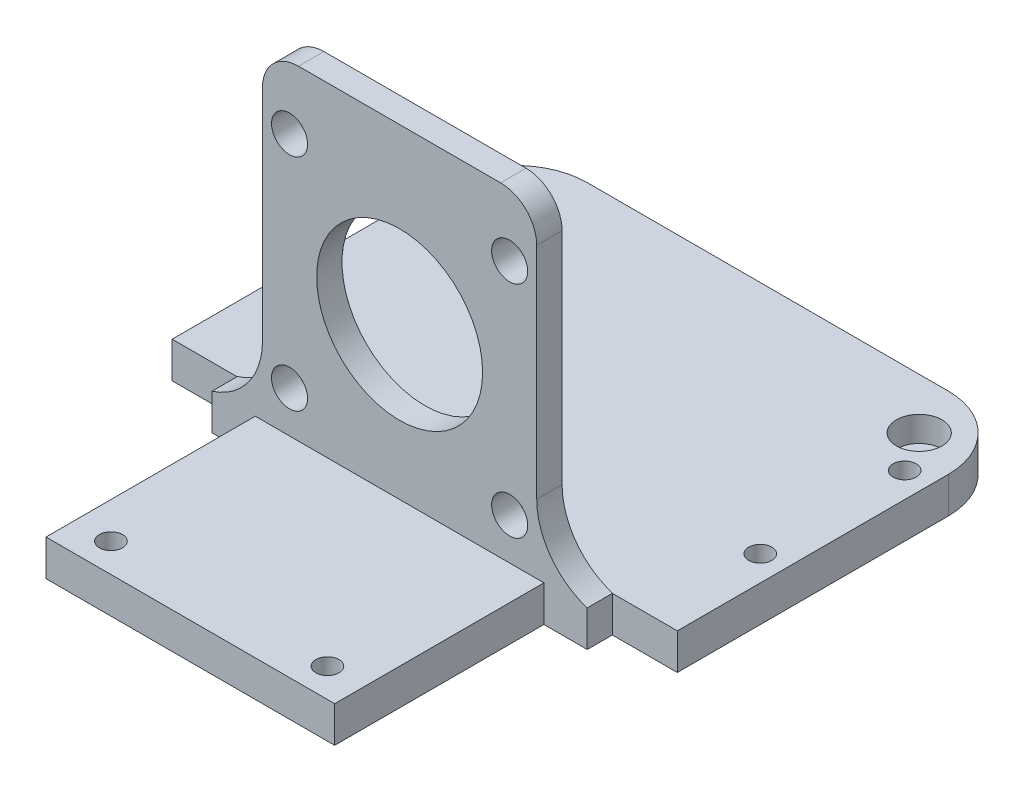
SolidWorks part; units mm, degrees
ref_plane "Front Plane" through (0, 0, 0) normal (0, 0, 1) x (1, 0, 0)
ref_plane "Top Plane" through (0, 0, 0) normal (0, 1, 0) x (1, 0, 0)
ref_plane "Right Plane" through (0, 0, 0) normal (1, 0, 0) x (0, 0, -1)
sketch "草图1" plane through (0, 0, 0) normal (0, 0, 1) x (1, 0, 0)
  line L1 (-35, 2.5) -> (35, 2.5)
  line L2 (-35, 2.5) -> (-35, -2.5)
  line L3 (-35, -2.5) -> (35, -2.5)
  line L4 (35, 2.5) -> (35, -2.5)
  line L5 (-35, 2.5) -> (35, -2.5) construction
  line L6 (-35, -2.5) -> (35, 2.5) construction
  point P0 (0, 0)
  dimension "D1" = 5
  dimension "D2" = 70
extrude "凸台-拉伸1" add sketch "草图1" along normal blind 8
sketch "草图2" plane through (0, 2.5, 0) normal (0, 1, 0) x (1, 0, 0)
  line L0 (0, 0) -> (0, -8) construction
  line L1 (35, -8) -> (-35, -8) construction
  circle A0 centre (-23.5, -4.24) radius 1.6424
  circle A1 centre (23.5, -4.24) radius 1.6424
  dimension "D1" = 23.5
  dimension "D2" = 3.76
extrude "切除-拉伸1" [suppressed] cut sketch "草图2" against normal blind 10
sketch "草图3" plane through (0, 0, 8) normal (0, 0, 1) x (1, 0, 0)
  line L0 (-35, -2.5) -> (35, -2.5) construction
  line L1 (-19, 2.5) -> (19, 2.5)
  line L2 (-19, 2.5) -> (-19, -2.5)
  line L3 (-19, -2.5) -> (19, -2.5)
  line L4 (19, 2.5) -> (19, -2.5)
  line L5 (-19, 2.5) -> (19, -2.5) construction
  line L6 (-19, -2.5) -> (19, 2.5) construction
  point P0 (0, 0)
  dimension "D1" = 38
extrude "凸台-拉伸2" add sketch "草图3" along normal blind 43
sketch "草图4" plane through (0, 2.5, 0) normal (0, 1, 0) x (1, 0, 0)
  line L0 (19, -51) -> (19, -8) construction
  line L1 (-19, -51) -> (19, -51)
  line L2 (-19, -51) -> (-19, -46)
  line L3 (-19, -46) -> (19, -46)
  line L4 (19, -51) -> (19, -46)
  dimension "D1" = 5
extrude "凸台-拉伸3" add sketch "草图4" along normal blind 45
sketch "草图5" plane through (0, 0, 51) normal (0, 0, 1) x (1, 0, 0)
  line L0 (-19, 2.5) -> (19, 2.5) construction
  line L1 (19, -2.5) -> (19, 47.5) construction
  line L2 (0, 2.5) -> (0, 44.5) construction
  circle A0 centre (0, 23.5) radius 11.5
  circle A1 centre (-15.25, 38.75) radius 1.6
  circle A2 centre (15.25, 38.75) radius 1.6
  circle A3 centre (-15.25, 8.25) radius 1.6
  circle A4 centre (15.25, 8.25) radius 1.6
  dimension "D2" = 23
  dimension "D7" = 3.2
  dimension "D1" = 42
  dimension "D3" = 15.25
  dimension "D4" = 15.25
  dimension "D5" = 15.25
  dimension "D6" = 30.5
extrude "切除-拉伸2" cut sketch "草图5" against normal blind 45
fillet "圆角1" radius 5 2 edges at (19, 47.5, 48.5) (-19, 47.5, 48.5)
sketch "草图6" plane through (0, 47.5, 0) normal (0, 1, 0) x (1, 0, 0)
  line L0 (-21, -47.4848) -> (-21, -9.4848) construction
  line L1 (21, -47.4848) -> (-21, -47.4848)
  line L2 (21, -47.4848) -> (21, -45.9222)
  line L3 (21, -45.9222) -> (-21, -45.9222)
  line L4 (-21, -47.4848) -> (-21, -45.9222)
extrude "切除-拉伸3" cut sketch "草图6" against normal up to surface (45 mm away) up to face at (0, 2.5, 15.5)
sketch "草图7" plane through (19, 0, 0) normal (1, 0, 0) x (0, 0, -1)
  line L0 (-37.9952, 2.5) -> (-37.9952, -2.5) construction
  line L1 (-51, -2.5) -> (-37.9952, -2.5)
  line L2 (-51, -2.5) -> (-51, 2.5)
  line L3 (-51, 2.5) -> (-37.9952, 2.5)
  line L4 (-37.9952, -2.5) -> (-37.9952, 2.5)
extrude "凸台-拉伸4" add sketch "草图7" along normal blind 7 and the other way blind 45
sketch "草图8" plane through (0, 2.5, 0) normal (0, 1, 0) x (1, 0, 0)
  circle A0 centre (23, -44.3286) radius 1.6
  circle A1 centre (-23, -44.3286) radius 1.6
  dimension "D1" = 3.2
extrude "切除-拉伸4" [suppressed] cut sketch "草图8" against normal blind 7
fillet "圆角2" radius 10 2 edges at (-19, 2.5, 49.2424) (19, 2.5, 49.2424)
sketch "草图9" plane through (0, 2.5, 0) normal (0, 1, 0) x (1, 0, 0)
  line L0 (-19, -8) -> (19, -8) construction
  line L1 (0, -8) -> (0, -37.9952) construction
  line L3 (-18.1552, -8) -> (18.1552, -8)
  line L4 (-18.1552, -8) -> (-18.1552, -37.9952)
  line L5 (-18.1552, -37.9952) -> (18.1552, -37.9952)
  line L6 (18.1552, -8) -> (18.1552, -37.9952)
  line L7 (-18.1552, -8) -> (18.1552, -37.9952) construction
  line L8 (-18.1552, -37.9952) -> (18.1552, -8) construction
  line L9 (-19, -8) -> (19, -8)
  line L10 (-19, -8) -> (-19, -37.9952)
  line L11 (-19, -37.9952) -> (19, -37.9952)
  line L12 (19, -8) -> (19, -37.9952)
  point P7 (0, -22.9976)
  line M9 (19, -37.9952) -> (19, -8)
  line M15 (-19, -8) -> (-19, -37.9952)
extrude "切除-拉伸5" [suppressed] cut sketch "草图9" against normal blind 10 contours L11 L4 L9 M15 | L6 L11 L9 M9
sketch "草图10" plane through (0, 0, 51) normal (0, 0, 1) x (1, 0, 0)
  circle A0 centre (-15.25, 38.75) radius 2.5
  circle A1 centre (0, 23.5) radius 21.5668 construction
  circle A2 centre (15.25, 38.75) radius 2.5
  circle A3 centre (15.25, 8.25) radius 2.5
  circle A4 centre (-15.25, 8.25) radius 2.5
  point P15 (0, 23.5)
  dimension "D1" = 5
  dimension "D2" = 4
sketch "草图13" plane through (0, 2.5, 0) normal (0, 1, 0) x (1, 0, 0)
  line L0 (0, 0) -> (0, -47.4848) construction
  line L1 (-14, -47.4848) -> (14, -47.4848) construction
  line L2 (-35, -8) -> (-35, 0) construction
  line L3 (-35, 0.0318) -> (35, 0.0318)
  line L4 (-35, 0.0318) -> (-35, -47.5165)
  line L5 (-35, -47.5165) -> (35, -47.5165)
  line L6 (35, 0.0318) -> (35, -47.5165)
  line L7 (-35, 0.0318) -> (35, -47.5165) construction
  line L8 (-35, -47.5165) -> (35, 0.0318) construction
  point P5 (0, -23.7424)
extrude "凸台-拉伸6" add sketch "草图13" against normal up to surface (5 mm away) up to face at (0, -2.5, 23.8317)
extrude "切除-拉伸6" cut sketch "草图10" against normal blind 10
sketch "草图11" plane through (0, 0, 51) normal (0, 0, 1) x (1, 0, 0)
  line L0 (0, 2.5) -> (0, 43.6627) construction
  line L2 (20, -2.5) -> (20, 2.5)
  line L3 (20, -2.5) -> (-20, -2.5)
  line L5 (20, 2.5) -> (-20, 2.5)
  line L6 (-20, -2.5) -> (-20, 2.5)
  dimension "D1" = 5
  dimension "D2" = 20
extrude "凸台-拉伸5" add sketch "草图11" along normal blind 29
sketch "草图12" plane through (0, 2.5, 0) normal (0, 1, 0) x (1, 0, 0)
  circle A0 centre (15, -76) radius 1.6
  circle A1 centre (-15, -76) radius 1.6
extrude "切除-拉伸7" cut sketch "草图12" against normal blind 7
sketch "草图14" plane through (0, 2.5, 0) normal (0, 1, 0) x (1, 0, 0)
  circle A0 centre (28, -7) radius 1.6
  circle A1 centre (-28, -7) radius 1.6
extrude "切除-拉伸8" cut sketch "草图14" against normal blind 7
sketch "草图15" plane through (0, 2.5, 0) normal (0, 1, 0) x (1, 0, 0)
  circle A0 centre (28, -7) radius 3.15
  circle A1 centre (-28, -7) radius 3.15
extrude "切除-拉伸9" cut sketch "草图15" against normal blind 3.5
fillet "圆角3" radius 10 2 edges at (35, 0, -0.0318) (-35, 0, -0.0318)
sketch "草图16" plane through (0, 2.5, 0) normal (0, 1, 0) x (1, 0, 0)
  circle A0 centre (31.5, -32.5186) radius 1.6
  circle A1 centre (31.5, -12.5186) radius 1.6
  circle A2 centre (-31.5, -32.5186) radius 1.6
  circle A3 centre (-31.5, -12.5186) radius 1.6
extrude "切除-拉伸10" cut sketch "草图16" against normal blind 10
